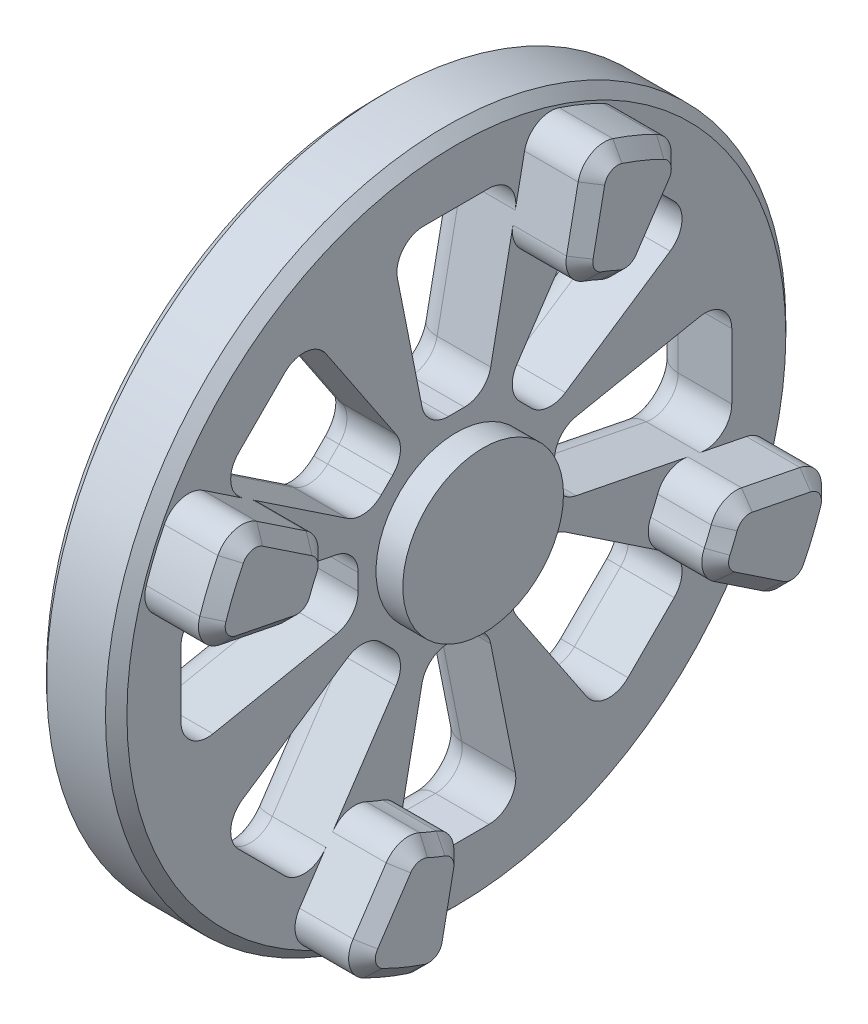
SolidWorks part; units mm, degrees
ref_plane "Спереди" through (0, 0, 0) normal (0, 0, 1) x (1, 0, 0)
ref_plane "Сверху" through (0, 0, 0) normal (0, 1, 0) x (1, 0, 0)
ref_plane "Справа" through (0, 0, 0) normal (1, 0, 0) x (0, 0, -1)
sketch "Sketch2" plane through (0, 0, 0) normal (1, 0, 0) x (0, 0, -1)
  circle A0 centre (0, 0) radius 3
  dimension "D1" = 6
extrude "Boss-Extrude1" add sketch "Sketch2" against normal blind 1 contours A0
sketch "Sketch4" plane through (-1, 0, 0) normal (-1, 0, 0) x (0, 0, 1)
  circle A0 centre (0, 0) radius 12.7
extrude "Фланец" add sketch "Sketch4" along normal blind 3 contours A0
chamfer "Chamfer2" distance 0.4 angle 45 2 edges at (-1, 0, 12.7) (-4, 0, 12.7)
sketch "Sketch6" plane through (-4, 0, 0) normal (-1, 0, 0) x (0, 0, 1)
  line L0 (0, -2.1126) -> (0, 14.8245) construction
  line L1 (-0.3011, 3.6663) -> (0.3011, 3.6663)
  line L2 (-1.2192, 10.2818) -> (1.2192, 10.2818)
  line L3 (2.2, 9.0868) -> (1.2819, 4.4712)
  line L4 (-2.2, 9.0868) -> (-1.2819, 4.4712)
  arc A0 (2.2, 9.0868) -> (1.2192, 10.2818) centre (1.2192, 9.2818) ccw
  arc A1 (1.2819, 4.4712) -> (0.3011, 3.6663) centre (0.3011, 4.6663) cw
  arc A2 (-2.2, 9.0868) -> (-1.2192, 10.2818) centre (-1.2192, 9.2818) cw
  arc A3 (-0.3011, 3.6663) -> (-1.2819, 4.4712) centre (-0.3011, 4.6663) cw
  point P9 (0, 10.2818)
  dimension "D3" = 1
  dimension "D1" = 1
  dimension "D2" = 11.25
extrude "Cut-Extrude6" cut sketch "Sketch6" against normal up to next
pattern_circular "CirPattern1" count 8 over 360 about axis through (0, 0, 0) along (1, 0, 0) of "Cut-Extrude6"
fillet "Fillet1" radius 1 64 edges at (-4, -0.9355, 3.8933) (-4, 0, 3.6663) (-4, 0.9355, 3.8933) (-4, 1.741, 6.779) (-4, 1.9923, 9.9162) (-4, 0, 10.2818) (-4, -1.9923, 9.9162) (-4, -3.4145, 2.0914) (-4, -2.5924, 2.5924) (-4, -2.0914, 3.4145) (-4, -3.5624, 6.0245) (-4, -5.6031, 8.4206) (-4, -7.2704, 7.2704) (-4, -8.4206, 5.6031) (-4, -3.8933, -0.9355) (-4, -3.6663, 0) (-4, -3.8933, 0.9355) (-4, -6.779, 1.741) (-4, -9.9162, 1.9923) (-4, -10.2818, 0) (-4, -9.9162, -1.9923) (-4, -2.0914, -3.4145) (-4, -2.5924, -2.5924) (-4, -3.4145, -2.0914) (-4, -6.0245, -3.5624) (-4, -8.4206, -5.6031) (-4, -7.2704, -7.2704) (-4, -5.6031, -8.4206) (-4, 0.9355, -3.8933) (-4, 0, -3.6663) (-4, -0.9355, -3.8933) (-4, -1.741, -6.779) (-4, -1.9923, -9.9162) (-4, 0, -10.2818) (-4, 1.9923, -9.9162) (-4, 3.4145, -2.0914) (-4, 2.5924, -2.5924) (-4, 2.0914, -3.4145) (-4, 3.5624, -6.0245) (-4, 5.6031, -8.4206) (-4, 7.2704, -7.2704) (-4, 8.4206, -5.6031) (-4, 9.9162, -1.9923) (-4, 10.2818, 0) (-4, 9.9162, 1.9923) (-4, 6.779, 1.741) (-4, 3.8933, 0.9355) (-4, 3.6663, 0) (-4, 3.8933, -0.9355) (-4, 8.4206, 5.6031) (-4, 7.2704, 7.2704) (-4, 5.6031, 8.4206) (-4, 3.5624, 6.0245) (-4, 2.0914, 3.4145) (-4, 2.5924, 2.5924) (-4, 3.4145, 2.0914) (-4, -1.741, 6.779) (-4, -6.0245, 3.5624) (-4, -6.779, -1.741) (-4, -3.5624, -6.0245) (-4, 1.741, -6.779) (-4, 6.0245, -3.5624) (-4, 6.779, -1.741) (-4, 6.0245, 3.5624)
sketch "Sketch10" plane through (-1, 0, 0) normal (1, 0, 0) x (0, 0, -1)
  line L0 (0, -0.5511) -> (0, 16.3859) construction
  line L6 (0, 0) -> (6.1734, 14.9039) construction
  line L8 (2.5459, 10.8254) -> (2.1125, 8.6468)
  line L9 (5.8545, 9.4549) -> (4.6204, 7.608)
  arc A5 (5.4715, 10.9042) -> (3.8415, 11.5794) centre (0, 0) ccw
  arc A10 (5.8545, 9.4549) -> (5.4715, 10.9042) centre (5.023, 10.0105) ccw
  arc A11 (3.8415, 11.5794) -> (2.5459, 10.8254) centre (3.5266, 10.6303) ccw
  arc A13 (3.368, 7.2565) -> (2.7496, 7.5126) centre (0, 0) ccw
  arc A14 (4.6204, 7.608) -> (3.368, 7.2565) centre (3.789, 8.1636) cw
  arc A15 (2.1125, 8.6468) -> (2.7496, 7.5126) centre (3.0933, 8.4517) ccw
  point P7 (6.4545, 10.3528)
  point P11 (2.7565, 11.8845)
  dimension "D1" = 1
  dimension "D2" = 1
extrude "Boss-Extrude7" add sketch "Sketch10" along a picked direction on the side of the normal blind 2.5
chamfer "Chamfer4" distance 0.5 angle 45 8 edges at (1.5, 10.2659, -5.9898) (1.5, 11.2713, -4.6687) (1.5, 11.4946, -3.0236) (1.5, 9.7361, -2.3292) (1.5, 7.962, -2.2214) (1.5, 7.391, -3.0615) (1.5, 7.2008, -4.0592) (1.5, 8.5314, -5.2375)
pattern_circular "CirPattern4" count 4 over 360 about axis through (0, 0, 0) along (1, 0, 0) of "Chamfer4", "Boss-Extrude7"
